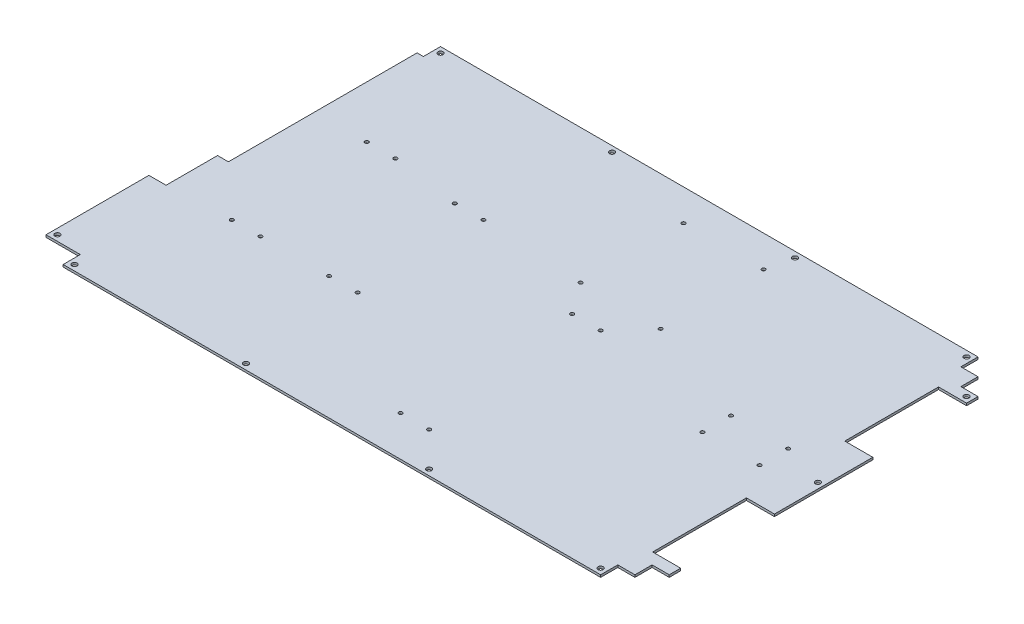
SolidWorks part; units mm, degrees
ref_plane "Front Plane" through (0, 0, 0) normal (0, 0, 1) x (1, 0, 0)
ref_plane "Top Plane" through (0, 0, 0) normal (0, 1, 0) x (1, 0, 0)
ref_plane "Right Plane" through (0, 0, 0) normal (1, 0, 0) x (0, 0, -1)
sketch "Sketch1" plane through (0, 0, 0) normal (0, 1, 0) x (1, 0, 0)
  line L0 (-250, -150) -> (-235, -150)
  line L1 (-250, -150) -> (250, -150) construction
  line L2 (-250, -150) -> (-250, 150) construction
  line L3 (-250, 150) -> (250, 150) construction
  line L4 (250, -150) -> (250, 150) construction
  line L5 (-250, -150) -> (250, 150) construction
  line L6 (-250, 150) -> (250, -150) construction
  line L7 (-235, -150) -> (-235, -165)
  line L8 (-235, -165) -> (235, -165)
  line L9 (235, -165) -> (235, -150)
  line L10 (235, -150) -> (250, -150)
  line L11 (250, -150) -> (250, -135)
  line L12 (250, -135) -> (265, -135)
  line L13 (265, -135) -> (265, 135)
  line L14 (265, 135) -> (250, 135)
  line L15 (250, 135) -> (250, 150)
  line L16 (250, 150) -> (235, 150)
  line L17 (235, 150) -> (235, 165)
  line L18 (235, 165) -> (-235, 165)
  line L19 (-235, 165) -> (-235, 150)
  line L20 (-235, 150) -> (-250, 150)
  line L21 (-250, 150) -> (-250, 135)
  line L22 (-250, 135) -> (-265, 135)
  line L23 (-265, 135) -> (-265, -135)
  line L24 (-265, -135) -> (-250, -135)
  line L25 (-250, -135) -> (-250, -150)
  point P0 (0, 0)
  dimension "D1" = 500
  dimension "D2" = 300
  dimension "D3" = 15
  dimension "D4" = 15
base flange "Base-Flange1" sketch "Sketch1" thickness 2 reverse thickness direction no parameters "D1"=1
sketch "Sketch3" plane through (0, 0, 0) normal (0, 1, 0) x (1, 0, 0)
  line L1 (-265, -135) -> (-250, -135)
  line L2 (-265, -135) -> (-265, -150)
  line L3 (-265, -150) -> (-250, -150)
  line L4 (-250, -135) -> (-250, -150)
base flange "Tab1" sketch "Sketch3" thickness 2 reverse thickness direction no parameters "D1"=1
sketch "Sketch4" plane through (0, 0, 0) normal (0, 1, 0) x (1, 0, 0)
  line L0 (-265, 135) -> (-265, -150) construction
  line L1 (-265, -15) -> (-250, -15)
  line L2 (-265, -15) -> (-265, -60)
  line L3 (-265, -60) -> (-250, -60)
  line L4 (-250, -15) -> (-250, -60)
  line L5 (-235, -165) -> (235, -165) construction
  dimension "D1" = 15
  dimension "D2" = 45
  dimension "D3" = 105
extrude "Cut-Extrude1" cut sketch "Sketch4" against normal up to next normal cut yes
hole_wizard "M4 Clearance Hole1" positions "Sketch5" profile "Sketch6" hole size "M4" standard "DIN" end condition up to next
sketch "Sketch5" plane through (0, 0, 0) normal (0, 1, 0) x (1, 0, 0)
  line L1 (-265, 135) -> (-265, -15) construction
  line L2 (-250, 135) -> (-265, 135) construction
  line L3 (-265, -150) -> (-235, -150) construction
  line L4 (-235, -165) -> (235, -165) construction
  line L5 (-235, -150) -> (-235, -165) construction
  line L6 (265, -135) -> (265, 135) construction
  line L7 (235, 165) -> (-235, 165) construction
  line L8 (235, -165) -> (235, -150) construction
  point P0 (-260, -145)
  point P2 (-260, 0)
  point P4 (-260, 130)
  point P6 (-230, 160)
  point P8 (-80, 160)
  point P10 (80, 160)
  point P12 (230, 160)
  point P14 (260, 130)
  point P16 (260, 0)
  point P18 (260, -145)
  point P20 (230, -160)
  point P22 (80, -160)
  point P24 (-80, -160)
  point P26 (-230, -160)
  dimension "D1" = 5
  dimension "D2" = 5
  dimension "D3" = 5
  dimension "D4" = 5
  dimension "D5" = 5
  dimension "D6" = 5
  dimension "D7" = 5
  dimension "D8" = 5
  dimension "D9" = 150
  dimension "D10" = 150
sketch "Sketch6" plane through (-260, 0, 145) normal (1, 0, 0) x (0, 0, 1)
  line L0 (0, 0) -> (0, 2)
  line L1 (0, 2) -> (2.25, 2)
  line L2 (2.25, 2) -> (2.25, 0)
  line L5 (2.25, 0) -> (0, 0)
  line L11 (0, -6.35) -> (0, 107.95) construction
  dimension "Thru Hole Dia." = 4.5
  dimension "Thru Hole Depth" = 2
hole_wizard "M3 Clearance Hole1" positions "Sketch8" profile "Sketch9" hole size "M3" standard "DIN" end condition up to next
sketch "Sketch8" plane through (0, 0, 0) normal (0, 1, 0) x (1, 0, 0)
  line L1 (171.5, 12.5) -> (221.5, 12.5) construction
  line L2 (171.5, 12.5) -> (171.5, -12.5) construction
  line L3 (171.5, -12.5) -> (221.5, -12.5) construction
  line L4 (221.5, 12.5) -> (221.5, -12.5) construction
  line L5 (265, -135) -> (265, 135) construction
  line L7 (75, 137.5) -> (5, 137.5) construction
  line L8 (75, 137.5) -> (75, 47.5) construction
  line L9 (75, 47.5) -> (5, 47.5) construction
  line L10 (5, 137.5) -> (5, 47.5) construction
  line L11 (235, 165) -> (-235, 165) construction
  line L13 (-85, 52.5) -> (-110, 52.5) construction
  line L14 (-85, 52.5) -> (-85, -57.5) construction
  line L15 (-85, -57.5) -> (-110, -57.5) construction
  line L16 (-110, 52.5) -> (-110, -57.5) construction
  line L18 (-170, -57.5) -> (-195, -57.5) construction
  line L19 (-170, -57.5) -> (-170, 60.5) construction
  line L20 (-170, 60.5) -> (-195, 60.5) construction
  line L21 (-195, -57.5) -> (-195, 60.5) construction
  line L22 (-265, 135) -> (-265, -15) construction
  line L24 (25, 20) -> (50, 20) construction
  line L25 (25, 20) -> (25, -130) construction
  line L26 (25, -130) -> (50, -130) construction
  line L27 (50, 20) -> (50, -130) construction
  line L28 (-235, -165) -> (235, -165) construction
  point P0 (221.5, -12.5)
  point P2 (171.5, -12.5)
  point P4 (171.5, 12.5)
  point P6 (221.5, 12.5)
  point P59 (171.5, 0)
  point P63 (75, 137.5)
  point P64 (5, 47.5)
  point P97 (75, 47.5)
  point P98 (5, 137.5)
  point P111 (-85, 52.5)
  point P115 (-110, -57.5)
  point P156 (-85, -57.5)
  point P157 (-110, 52.5)
  point P168 (-170, -57.5)
  point P169 (-195, 60.5)
  point P246 (-170, 60.5)
  point P247 (-195, -57.5)
  point P250 (25, 20)
  point P251 (50, -130)
  point P308 (25, -130)
  point P309 (50, 20)
  dimension "D1" = 43.5
  dimension "D2" = 50
  dimension "D3" = 25
  dimension "D4" = 70
  dimension "D5" = 90
  dimension "D6" = 27.5
  dimension "D7" = 190
  dimension "D8" = 110
  dimension "D9" = 25
  dimension "D10" = 112.5
  dimension "D11" = 350
  dimension "D12" = 25
  dimension "D13" = 118
  dimension "D14" = 70
  dimension "D15" = 215
  dimension "D16" = 25
  dimension "D17" = 150
  dimension "D18" = 35
sketch "Sketch9" plane through (221.5, 0, 12.5) normal (1, 0, 0) x (0, 0, 1)
  line L0 (0, 0) -> (0, 2)
  line L1 (0, 2) -> (1.6, 2)
  line L2 (1.6, 2) -> (1.6, 0)
  line L5 (1.6, 0) -> (0, 0)
  line L11 (0, -6.35) -> (0, 107.95) construction
  dimension "Thru Hole Dia." = 3.2
  dimension "Thru Hole Depth" = 2
sketch "Sketch10" plane through (0, 0, 0) normal (0, 1, 0) x (1, 0, 0)
  line L0 (265, -135) -> (265, 135) construction
  line L1 (265, 125) -> (240.5, 125)
  line L2 (265, 125) -> (265, 43)
  line L3 (265, 43) -> (240.5, 43)
  line L4 (240.5, 125) -> (240.5, 43)
  line L5 (265, 135) -> (250, 135) construction
  line L6 (265, -43) -> (240.5, -43)
  line L7 (265, -43) -> (265, -125)
  line L8 (265, -125) -> (240.5, -125)
  line L9 (240.5, -43) -> (240.5, -125)
  line L10 (250, -135) -> (265, -135) construction
  dimension "D1" = 10
  dimension "D2" = 82
  dimension "D3" = 10
  dimension "D4" = 24.5
extrude "Cut-Extrude2" cut sketch "Sketch10" against normal up to next normal cut yes
sketch "Sketch11" plane through (0, 0, 0) normal (0, 1, 0) x (1, 0, 0)
  line L0 (-265, 135) -> (-265, -15) construction
  line L1 (-265, 150) -> (-240.5, 150)
  line L2 (-265, 150) -> (-265, -15)
  line L3 (-265, -15) -> (-240.5, -15)
  line L4 (-240.5, 150) -> (-240.5, -15)
  line L5 (-235, 150) -> (-250, 150) construction
  point P6 (-265, 126.3817)
  point P7 (-239.0438, 150)
  point P10 (-265, -15)
  dimension "D1" = 24.5
extrude "Cut-Extrude3" cut sketch "Sketch11" against normal up to next normal cut yes
sketch "Bend-Lines1" [suppressed] plane through (0, 0, 0) normal (0, 1, 0) x (1, 0, 0)
sketch "Bounding-Box1" [suppressed] plane through (0, 0, 0) normal (0, 1, 0) x (1, 0, 0)
sheet metal parameters "Sheet-Metal1" thickness 2 parameters "D1"=1
flat pattern "Flat-Pattern1" [suppressed]
sketch "Bend-Lines2" plane through (0, 0, 0) normal (0, 1, 0) x (1, 0, 0)
sketch3d "Bounding-Box2" [suppressed]
  line L0 (265, 165, 0) -> (-265, 165, 0) construction
  line L1 (265, -165, 0) -> (-265, -165, 0) construction
  line L2 (265, 165, 0) -> (265, -165, 0) construction
  line L3 (-265, 165, 0) -> (-265, -165, 0) construction
sheet metal parameters "Sheet-Metal3" thickness 2 parameters "D1"=1
flat pattern "Flat-Pattern3"
sketch "Bend-Lines3" plane through (0, 0, 0) normal (0, 1, 0) x (1, 0, 0)
sketch3d "Bounding-Box3" [suppressed]
  line L0 (265, 165, 0) -> (-265, 165, 0) construction
  line L1 (265, -165, 0) -> (-265, -165, 0) construction
  line L2 (265, 165, 0) -> (265, -165, 0) construction
  line L3 (-265, 165, 0) -> (-265, -165, 0) construction
sheet metal parameters "Sheet-Metal4" thickness 2 parameters "D1"=1
flat pattern "Flat-Pattern3"
sketch "Bend-Lines3" plane through (0, 0, 0) normal (0, 1, 0) x (1, 0, 0)
sketch3d "Bounding-Box3" [suppressed]
  line L0 (265, 165, 0) -> (-265, 165, 0) construction
  line L1 (265, -165, 0) -> (-265, -165, 0) construction
  line L2 (265, 165, 0) -> (265, -165, 0) construction
  line L3 (-265, 165, 0) -> (-265, -165, 0) construction
sheet metal parameters "Sheet-Metal5" thickness 2 parameters "D1"=1
flat pattern "Flat-Pattern3"
sketch "Bend-Lines3" plane through (0, 0, 0) normal (0, 1, 0) x (1, 0, 0)
sketch3d "Bounding-Box3" [suppressed]
  line L0 (265, 165, 0) -> (-265, 165, 0) construction
  line L1 (265, -165, 0) -> (-265, -165, 0) construction
  line L2 (265, 165, 0) -> (265, -165, 0) construction
  line L3 (-265, 165, 0) -> (-265, -165, 0) construction
sheet metal parameters "Sheet-Metal6" thickness 2 parameters "D1"=1
flat pattern "Flat-Pattern3"
sketch "Bend-Lines3" plane through (0, 0, 0) normal (0, 1, 0) x (1, 0, 0)
sketch3d "Bounding-Box3" [suppressed]
  line L0 (265, 165, 0) -> (-265, 165, 0) construction
  line L1 (265, -165, 0) -> (-265, -165, 0) construction
  line L2 (265, 165, 0) -> (265, -165, 0) construction
  line L3 (-265, 165, 0) -> (-265, -165, 0) construction
sheet metal parameters "Sheet-Metal7" thickness 2 parameters "D1"=1
flat pattern "Flat-Pattern3"
sketch "Bend-Lines3" plane through (0, 0, 0) normal (0, 1, 0) x (1, 0, 0)
sketch3d "Bounding-Box3" [suppressed]
  line L0 (265, 165, 0) -> (-265, 165, 0) construction
  line L1 (265, -165, 0) -> (-265, -165, 0) construction
  line L2 (265, 165, 0) -> (265, -165, 0) construction
  line L3 (-265, 165, 0) -> (-265, -165, 0) construction
sheet metal parameters "Sheet-Metal8" thickness 2 parameters "D1"=1
flat pattern "Flat-Pattern3"
sketch "Bend-Lines3" plane through (0, 0, 0) normal (0, 1, 0) x (1, 0, 0)
sketch3d "Bounding-Box3" [suppressed]
  line L0 (265, 165, 0) -> (-265, 165, 0) construction
  line L1 (265, -165, 0) -> (-265, -165, 0) construction
  line L2 (265, 165, 0) -> (265, -165, 0) construction
  line L3 (-265, 165, 0) -> (-265, -165, 0) construction
